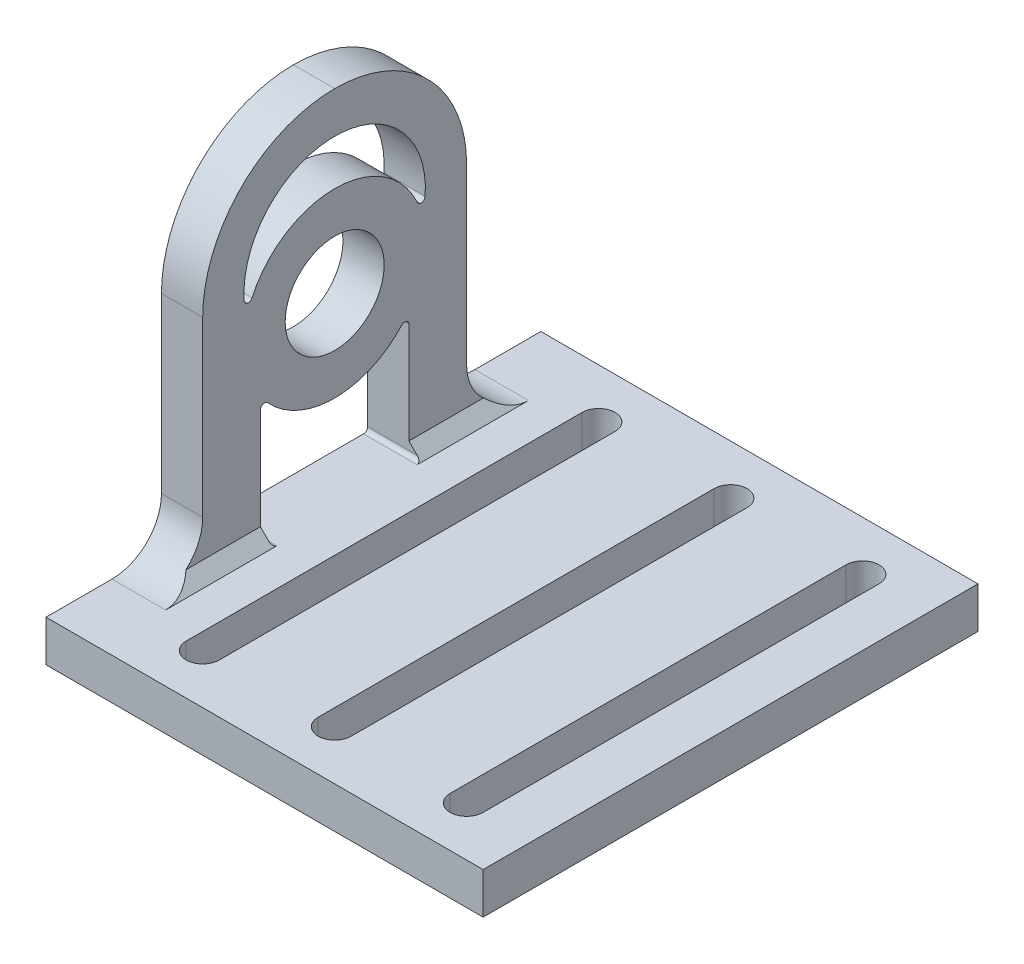
SolidWorks part; units mm, degrees
material "PMMA"
ref_plane "Front Plane" through (0, 0, 0) normal (0, 0, 1) x (1, 0, 0)
ref_plane "Top Plane" through (0, 0, 0) normal (0, 1, 0) x (1, 0, 0)
ref_plane "Right Plane" through (0, 0, 0) normal (1, 0, 0) x (0, 0, -1)
sketch "Sketch1" plane through (0, 0, 0) normal (0, 1, 0) x (1, 0, 0)
  line L0 (0, 0) -> (48, 0)
  line L1 (48, 0) -> (48, -60)
  line L2 (48, -60) -> (0, -60)
  line L3 (0, -60) -> (0, 0)
  line L4 (24, 0) -> (24, -60) construction
  line L5 (8, 0) -> (8, -60) construction
  line L6 (8, -6) -> (8, -54) construction
  line L7 (10, -6) -> (10, -54)
  line L8 (6, -6) -> (6, -54)
  line L9 (40, -6) -> (40, -54) construction
  line L10 (38, -6) -> (38, -54)
  line L11 (42, -6) -> (42, -54)
  line L12 (24, -6) -> (24, -54) construction
  line L13 (26, -6) -> (26, -54)
  line L14 (22, -6) -> (22, -54)
  arc A0 (10, -6) -> (6, -6) centre (8, -6) ccw
  arc A1 (6, -54) -> (10, -54) centre (8, -54) ccw
  arc A2 (38, -6) -> (42, -6) centre (40, -6) cw
  arc A3 (42, -54) -> (38, -54) centre (40, -54) cw
  arc A4 (26, -6) -> (22, -6) centre (24, -6) ccw
  arc A5 (22, -54) -> (26, -54) centre (24, -54) ccw
  point P11 (8, -30)
  point P18 (40, -30)
  point P25 (24, -30)
  point P28 (24, -54)
  point P29 (24, -6)
  dimension "D4" = 2
  dimension "D7" = 2
  dimension "D1" = 48
  dimension "D2" = 60
  dimension "D5" = 6
  dimension "D6" = 6
  dimension "D3" = 16
extrude "Boss-Extrude1" add sketch "Sketch1" along normal blind 5
sketch "Sketch2" plane through (0, 0, 0) normal (-1, 0, 0) x (0, 0, 1)
  line L0 (0, 5) -> (60, 5)
  line L1 (60, 5) -> (60, 0)
  line L2 (60, 0) -> (0, 0)
  line L3 (0, 0) -> (0, 5)
extrude "Boss-Extrude2" add sketch "Sketch2" along normal blind 5
sketch "Sketch4" plane through (0, 5, 0) normal (0, 1, 0) x (1, 0, 0)
  line L0 (-5, -14) -> (0, -14)
  line L1 (-5, -60) -> (-5, 0) construction
  line L2 (0, -14) -> (0, -46)
  line L3 (0, -46) -> (-5, -46)
  line L4 (-5, -46) -> (-5, -14)
  line L5 (48, 0) -> (-5, 0) construction
  line L6 (-5, -60) -> (48, -60) construction
  dimension "D1" = 14
  dimension "D2" = 14
extrude "Boss-Extrude3" add sketch "Sketch4" along normal blind 43
fillet "Fillet2" radius 6 2 edges at (-2.5, 5, 46) (-2.5, 5, 14)
chamfer "Chamfer1" distance 1.5 angle 45 1 edges at (0, 5, 30)
sketch "Sketch6" plane through (-5, 0, 0) normal (-1, 0, 0) x (0, 0, 1)
  line L0 (8, 5) -> (52, 5) construction
  line L1 (46, 11) -> (46, 1.7438) construction
  line L2 (14, 11) -> (14, 2.2022) construction
  line L3 (14, 48) -> (14, 11) construction
  line L4 (14, 48) -> (46, 5) construction
  line L5 (46, 48) -> (14, 5) construction
  arc A0 (8, 5) -> (14, 11) centre (8, 11) ccw construction
  circle A1 centre (30, 26.5) radius 6
  dimension "D1" = 12
extrude "Cut-Extrude1" cut sketch "Sketch6" against normal through all
fillet "Fillet3" radius 16 2 edges at (-2.5, 48, 46) (-2.5, 48, 14)
sketch "Sketch7" plane through (-5, 0, 0) normal (-1, 0, 0) x (0, 0, 1)
  line L0 (21, 18.754) -> (21, 5.5)
  line L1 (14, 32) -> (14, 11) construction
  line L2 (39, 18.754) -> (39, 5.5)
  line L3 (46, 32) -> (46, 11) construction
  line L4 (21.5, 5) -> (38.5, 5)
  line L5 (0, 0) -> (60, 0) construction
  arc A0 (40.9719, 31.2143) -> (19.0281, 31.2143) centre (30, 32) ccw
  arc A1 (46, 32) -> (30, 48) centre (30, 32) ccw construction
  arc A2 (40.0178, 31.0435) -> (19.9822, 31.0435) centre (30, 26.5) ccw
  circle A3 centre (30, 26.5) radius 6 construction
  arc A4 (40.0178, 31.0435) -> (40.9719, 31.2143) centre (40.4732, 31.25) ccw
  arc A5 (19.9822, 31.0435) -> (19.0281, 31.2143) centre (19.5268, 31.25) cw
  arc A6 (21.8696, 19.0908) -> (38.1304, 19.0908) centre (30, 26.5) ccw
  arc A7 (38.5, 5) -> (39, 5.5) centre (38.5, 5.5) ccw
  arc A8 (21.5, 5) -> (21, 5.5) centre (21.5, 5.5) cw
  arc A9 (39, 18.754) -> (38.1304, 19.0908) centre (38.5, 18.754) ccw
  arc A10 (21, 18.754) -> (21.8696, 19.0908) centre (21.5, 18.754) cw
  dimension "D1" = 5
  dimension "D2" = 5
  dimension "D3" = 0.5
  dimension "D4" = 11
  dimension "D8" = 0.5
  dimension "D5" = 7
  dimension "D6" = 7
  dimension "D7" = 5
extrude "Cut-Extrude2" cut sketch "Sketch7" against normal through all
